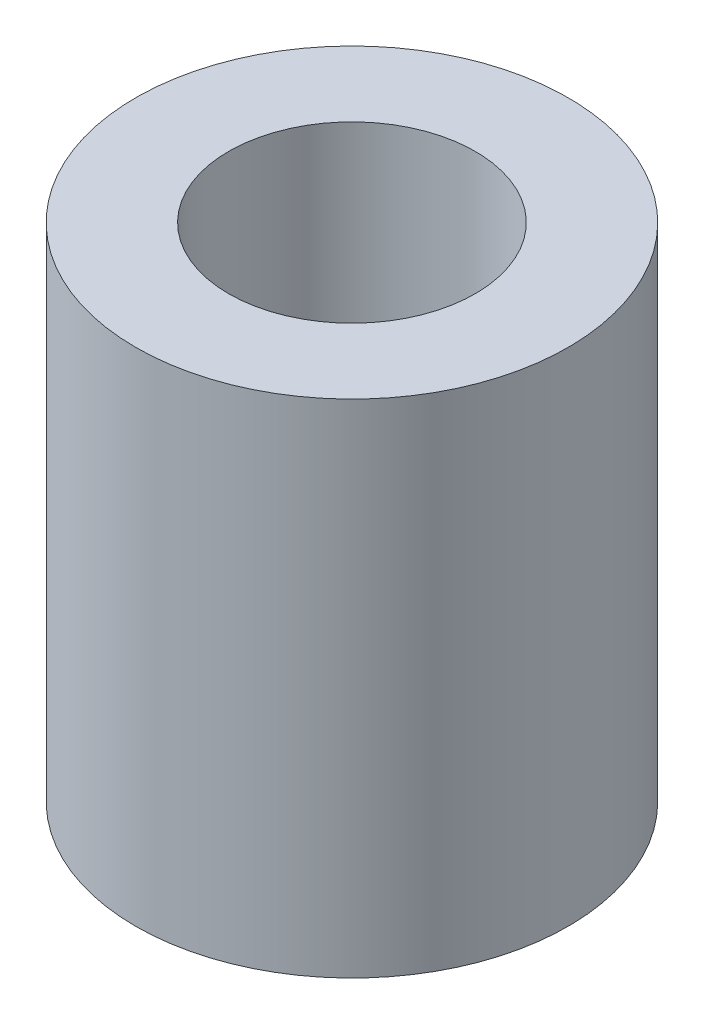
SolidWorks part; units mm, degrees
ref_plane "Front Plane" through (0, 0, 0) normal (0, 0, 1) x (1, 0, 0)
ref_plane "Top Plane" through (0, 0, 0) normal (0, 1, 0) x (1, 0, 0)
ref_plane "Right Plane" through (0, 0, 0) normal (1, 0, 0) x (0, 0, -1)
sketch "Sketch1" plane through (0, 0, 0) normal (0, 1, 0) x (1, 0, 0)
  circle A0 centre (0, 0) radius 6.9
  dimension "D1" = 13.8
extrude "Boss-Extrude1" add sketch "Sketch1" along normal blind 16
sketch "Sketch2" plane through (0, 16, 0) normal (0, 1, 0) x (1, 0, 0)
  circle A0 centre (0, 0) radius 3.935
  dimension "D1" = 7.87
extrude "Cut-Extrude1" cut sketch "Sketch2" against normal offset from surface (14 mm away) 2 up to face at (0, 0, 6.9)
